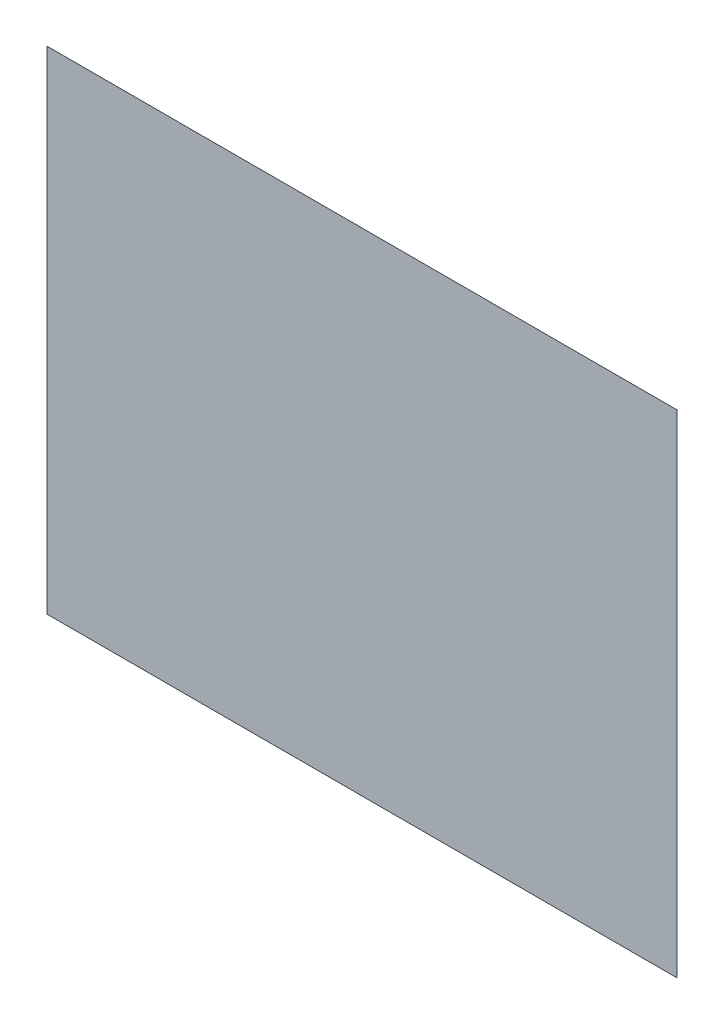
SolidWorks part; units mm, degrees
ref_plane "前视基准面" through (0, 0, 0) normal (0, 0, 1) x (1, 0, 0)
ref_plane "上视基准面" through (0, 0, 0) normal (0, 1, 0) x (1, 0, 0)
ref_plane "右视基准面" through (0, 0, 0) normal (1, 0, 0) x (0, 0, -1)
sketch "草图1" plane through (0, 0, 0) normal (0, 0, 1) x (1, 0, 0)
  line L0 (107.0902, 126.3962) -> (-17.0814, 126.3962) construction
  line L1 (-22.4956, 126.3962) -> (112.5044, 126.3962)
  line L2 (-22.4956, 126.3962) -> (-22.4956, 1.3962)
  line L3 (-22.4956, 1.3962) -> (112.5044, 1.3962)
  line L4 (112.5044, 126.3962) -> (112.5044, 1.3962)
  line L5 (-22.4956, 120.982) -> (-22.4956, 94.3104) construction
  line L6 (112.5044, 94.3104) -> (112.5044, 120.982) construction
  line L7 (-17.0814, 1.3962) -> (107.0902, 1.3962) construction
ref_plane "基准面1" through (0, 0, 100) normal (0, 0, 1) x (1, 0, 0)
sketch "草图2" plane through (0, 0, 100) normal (0, 0, 1) x (1, 0, 0)
  line L0 (-22.4956, 126.3962) -> (112.5044, 126.3962) construction
  line L1 (-122.4956, 226.3962) -> (212.5044, 226.3962)
  line L2 (-122.4956, 226.3962) -> (-122.4956, -35.0038)
  line L3 (-122.4956, -35.0038) -> (212.5044, -35.0038)
  line L4 (212.5044, 226.3962) -> (212.5044, -35.0038)
  line L5 (112.5044, 126.3962) -> (112.5044, 1.3962) construction
  line L6 (-22.4956, 126.3962) -> (-22.4956, 1.3962) construction
  line L7 (-22.4956, 1.3962) -> (112.5044, 1.3962) construction
  dimension "D1" = 100
  dimension "D2" = 100
  dimension "D3" = 100
  dimension "D4" = 36.4
loft "放样1" add profiles "草图2", "草图1" connector at (-122.4956, 226.3962, 100) connector at (-22.4956, 126.3962, 0)
